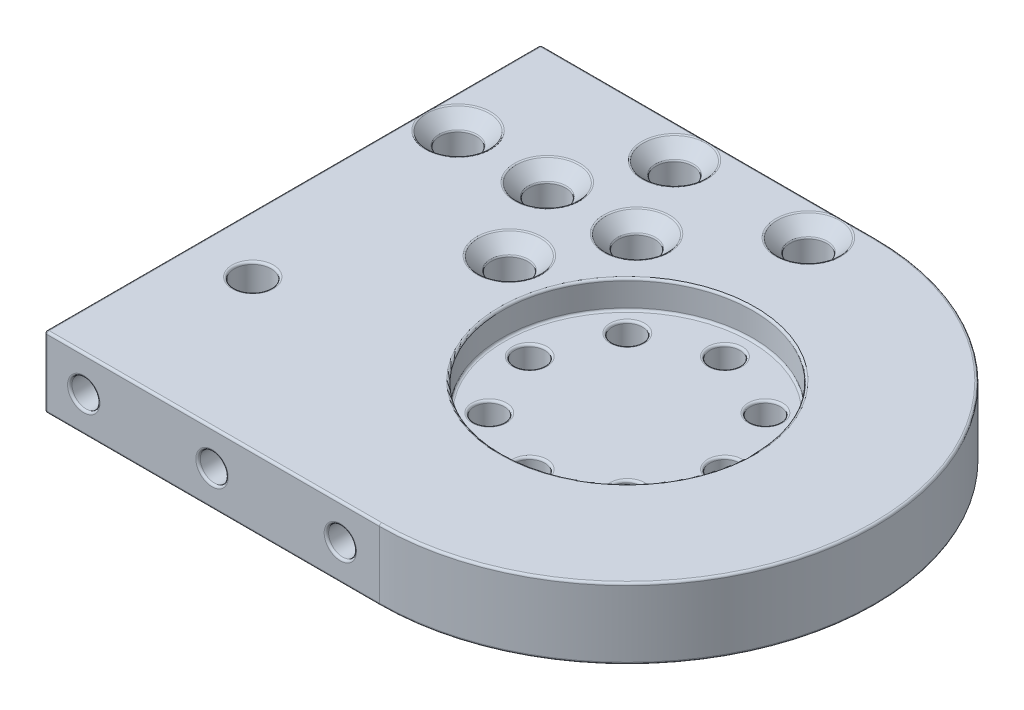
SolidWorks part; units mm, degrees
ref_plane "Front Plane" through (0, 0, 0) normal (0, 0, 1) x (1, 0, 0)
ref_plane "Top Plane" through (0, 0, 0) normal (0, 1, 0) x (1, 0, 0)
ref_plane "Right Plane" through (0, 0, 0) normal (1, 0, 0) x (0, 0, -1)
sketch "Sketch1" plane through (0, 0, 0) normal (0, 1, 0) x (1, 0, 0)
  line L0 (0, 44.45) -> (-60, 44.45)
  line L1 (-60, 44.45) -> (-60, -44.45)
  line L2 (-60, -44.45) -> (0, -44.45)
  line L3 (0, 0) -> (17.5, 0) construction
  line L4 (-38, 23.65) -> (-22, 23.65) construction
  line L5 (-30, 38.45) -> (-30, 23.65) construction
  line L6 (-30, 23.65) -> (-30, 8.85) construction
  line L7 (-6, 38.45) -> (-30, 38.45) construction
  line L8 (-38, 23.65) -> (-54, 23.65) construction
  arc A0 (0, -44.45) -> (0, 44.45) centre (0, 0) ccw
  circle A1 centre (17.5, 0) radius 2.7
  circle A2 centre (12.3744, -12.3744) radius 2.7
  circle A3 centre (0, -17.5) radius 2.7
  circle A4 centre (-12.3744, -12.3744) radius 2.7
  circle A5 centre (-17.5, 0) radius 2.7
  circle A6 centre (-12.3744, 12.3744) radius 2.7
  circle A7 centre (0, 17.5) radius 2.7
  circle A8 centre (12.3744, 12.3744) radius 2.7
  circle A9 centre (0, 0) radius 22.5
  circle A10 centre (-30, 38.45) radius 3.3
  circle A11 centre (-30, 8.85) radius 3.3
  circle A12 centre (-22, 23.65) radius 3.3
  circle A13 centre (-38, 23.65) radius 3.3
  circle A14 centre (-6, 38.45) radius 3.3
  circle A15 centre (-54, 23.65) radius 3.3
  circle A16 centre (-49.69, -17.46) radius 3.3
  point P26 (0, 0)
  dimension "D1" = 88.9
  dimension "D3" = 17.5
  dimension "D4" = 5.4
  dimension "D6" = 45
  dimension "D7" = 61.91
  dimension "D14" = 6.6
  dimension "D15" = 10.31
  dimension "D2" = 60
  dimension "D5" = 8
  dimension "D8" = 6
  dimension "D9" = 30
  dimension "D10" = 22
  dimension "D11" = 6
  dimension "D12" = 20.8
  dimension "D13" = 54
extrude "Boss-Extrude1" add sketch "Sketch1" against normal blind 12.7 contours L2 A0 L0 L1 A16 A15 A14 A13 A12 A11 A10 A9 | A9 A1 A2 A3 A4 A5 A6 A7 A8 region at (43.0784, 0, 0) region at (0, 0, 0)
chamfer "Chamfer2" distance 2.4 angle 45 6 edges at (-6, 0, -35.15) (-30, 0, -5.55) (-22, 0, -20.35) (-30, 0, -35.15) (-38, 0, -20.35) (-54, 0, -20.35)
extrude "Cut-Extrude1" cut sketch "Sketch1<3>" against normal blind 5 contours A9
sketch "Sketch1<3>" plane through (0, 0, 0) normal (0, 1, 0) x (1, 0, 0) same geometry as "Sketch1"
sketch "Sketch2" plane through (0, 0, 44.45) normal (0, 0, 1) x (1, 0, 0)
  line L0 (-60, -6.35) -> (-53, -6.35) construction
  line L1 (-60, -12.7) -> (-60, 0) construction
  line L2 (-53, -6.35) -> (-30, -6.35) construction
  line L3 (-30, -6.35) -> (-7, -6.35) construction
  circle A0 centre (-7, -6.35) radius 2.5
  circle A1 centre (-30, -6.35) radius 2.5
  circle A2 centre (-53, -6.35) radius 2.5
  dimension "D1" = 30
  dimension "D4" = 5
  dimension "D2" = 7
  dimension "D3" = 53
extrude "Cut-Extrude2" cut sketch "Sketch2" against normal blind 10
fillet "Fillet1" radius 0.4 54 edges at (-54, -2.4, -20.35) (-22, -2.4, -20.35) (-6, -2.4, -35.15) (-30, -2.4, -35.15) (-38, -2.4, -20.35) (-30, -2.4, -5.55) (-17.5, -5, 2.7) (-12.3744, -5, 15.0744) (0, -5, 20.2) (12.3744, -5, 15.0744) (17.5, -5, 2.7) (12.3744, -5, -9.6744) (0, -5, -14.8) (-12.3744, -5, -9.6744) (-50.5, -6.35, 44.45) (-50.5, -6.35, 34.45) (-27.5, -6.35, 44.45) (-27.5, -6.35, 34.45) (-4.5, -6.35, 44.45) (-4.5, -6.35, 34.45) (-60, 0, 0) (-30, 0, -44.45) (44.45, 0, 0) (-30, 0, 44.45) (-49.69, 0, 20.76) (-54, 0, -17.95) (-38, 0, -17.95) (-30, 0, -32.75) (-22, 0, -17.95) (-30, 0, -3.15) (-6, 0, -32.75) (0, 0, 22.5) (12.3744, -12.7, -9.6744) (0, -12.7, -14.8) (-12.3744, -12.7, -9.6744) (-17.5, -12.7, 2.7) (-12.3744, -12.7, 15.0744) (0, -12.7, 20.2) (12.3744, -12.7, 15.0744) (17.5, -12.7, 2.7) (44.45, -12.7, 0) (-30, -12.7, -44.45) (-60, -12.7, 0) (-30, -12.7, 44.45) (-30, -12.7, -35.15) (-30, -12.7, -5.55) (-22, -12.7, -20.35) (-38, -12.7, -20.35) (-6, -12.7, -35.15) (-54, -12.7, -20.35) (-49.69, -12.7, 20.76) (0, -5, 22.5) (-60, -6.35, 44.45) (-60, -6.35, -44.45)
